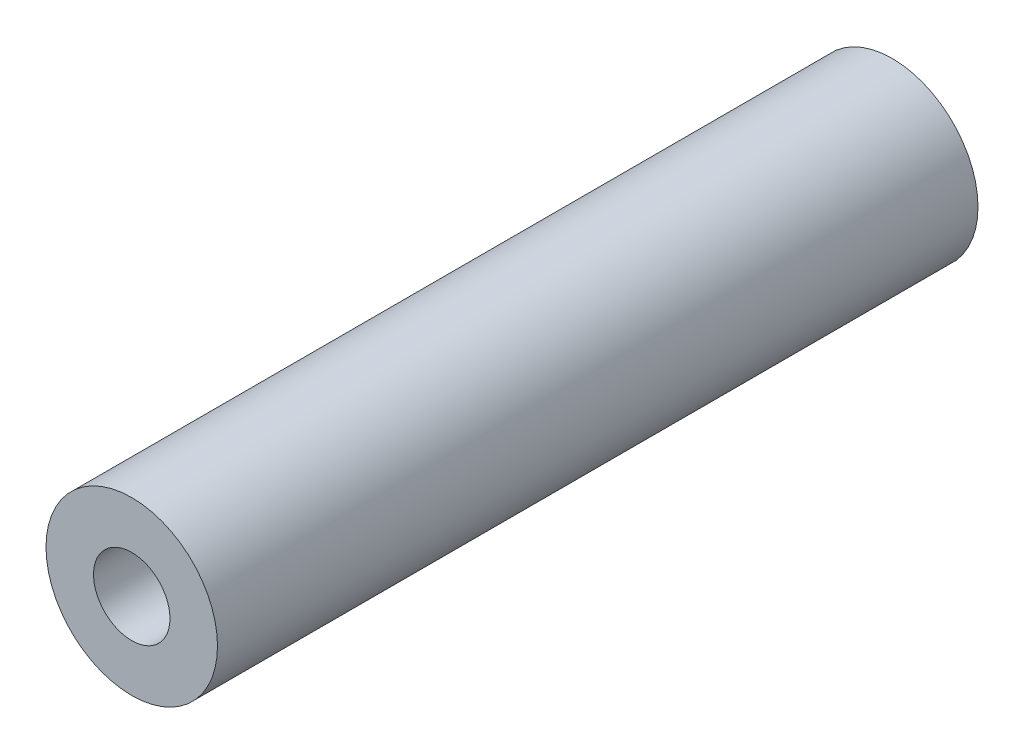
SolidWorks part; units mm, degrees
material "6061-T6 (SS)"
ref_plane "Front Plane" through (0, 0, 0) normal (0, 0, 1) x (1, 0, 0)
ref_plane "Top Plane" through (0, 0, 0) normal (0, 1, 0) x (1, 0, 0)
ref_plane "Right Plane" through (0, 0, 0) normal (1, 0, 0) x (0, 0, -1)
sketch "Sketch1" plane through (0, 0, 0) normal (0, 0, 1) x (1, 0, 0)
  circle A0 centre (0, 0) radius 2.5527
  circle A1 centre (0, 0) radius 5.7277
  dimension "D1" = 5.1054
  dimension "D2" = 3.175
extrude "Boss-Extrude1" add sketch "Sketch1" along normal blind 50.8
